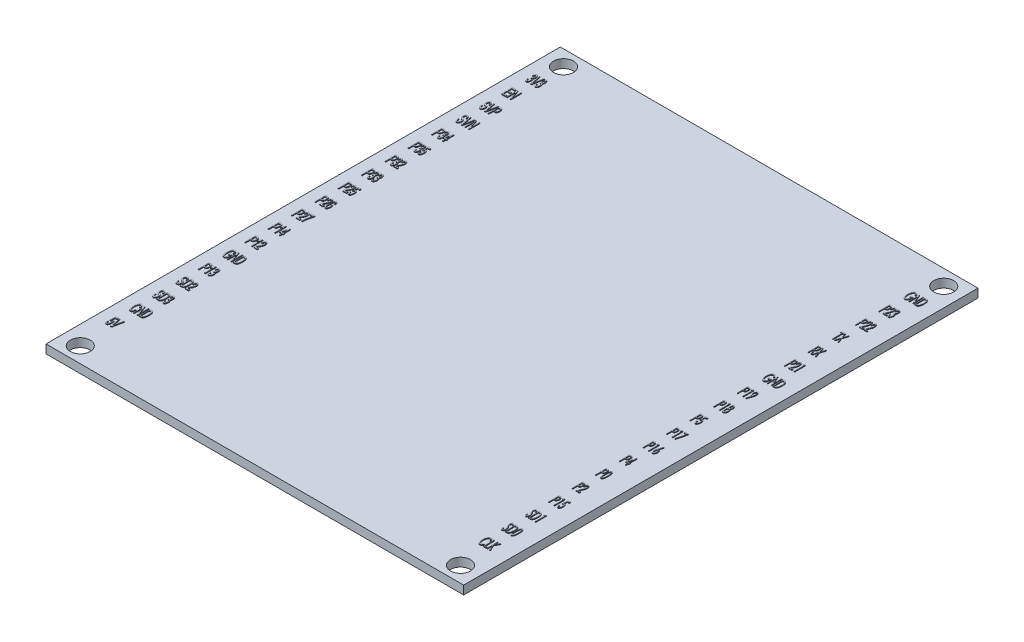
SolidWorks part; units mm, degrees
ref_plane "Front Plane" through (0, 0, 0) normal (0, 0, 1) x (1, 0, 0)
ref_plane "Top Plane" through (0, 0, 0) normal (0, 1, 0) x (1, 0, 0)
ref_plane "Right Plane" through (0, 0, 0) normal (1, 0, 0) x (0, 0, -1)
sketch "Sketch1" plane through (0, 0, 0) normal (0, 1, 0) x (1, 0, 0)
  line L1 (0, 0) -> (63.1, 0)
  line L2 (0, 0) -> (0, -77.7)
  line L3 (0, -77.7) -> (63.1, -77.7)
  line L4 (63.1, 0) -> (63.1, -77.7)
  dimension "D1" = 63.1
  dimension "D2" = 77.7
extrude "Boss-Extrude1" add sketch "Sketch1" along normal blind 1.3
sketch "Sketch2" plane through (0, 1.3, 0) normal (0, 1, 0) x (1, 0, 0)
  line L0 (0, 0) -> (1.5556, -1.5556) construction
  line L1 (0, -38.85) -> (63.1, -38.85) construction
  line L2 (0, 0) -> (0, -77.7) construction
  line L3 (63.1, -77.7) -> (63.1, 0) construction
  line L4 (31.55, -77.7) -> (31.55, 0) construction
  line L5 (0, -77.7) -> (63.1, -77.7) construction
  line L6 (63.1, 0) -> (0, 0) construction
  circle A0 centre (2.8308, -2.3456) radius 1.5
  circle A1 centre (2.8308, -75.3544) radius 1.5
  circle A2 centre (60.2692, -2.3456) radius 1.5
  circle A3 centre (60.2692, -75.3544) radius 1.5
  dimension "D2" = 3
  dimension "D1" = 2.2
extrude "Cut-Extrude1" cut sketch "Sketch2" against normal up to surface (1.3 mm away) up to face at (31.55, 0, 38.85)
sketch "Sketch3" plane through (0, 1.3, 0) normal (0, 1, 0) x (1, 0, 0)
  line L0 (63.1, -77.7) -> (63.1, 0) construction
  line L1 (58.6033, -7) -> (63.1, -7)
  text T0 "3V3\r\nEN\r\nSVP\r\nSVN\r\nP34\r\nP35\r\nP32\r\nP33\r\nP25\r\nP26\r\nP27\r\nP14\r\nP12\r\nGND\r\nP13\r\nSD2\r\nSD3\r\nCND\r\n5V" font "Arial" height 1.641
  text T1 "GND\r\nP23\r\nP22\r\nTX\r\nRX\r\nP21\r\nGND\r\nP19\r\nP18\r\nP5\r\nP17\r\nP16\r\nP4\r\nP0\r\nP2\r\nP15\r\nSD1\r\nSD0\r\nCLK" font "Century Gothic" height 1.6
sketch "Sketch4" plane through (0, 1.3, 0) normal (0, 1, 0) x (1, 0, 0)
  line L0 (58.8567, -7.1455) -> (1.6968, -7.1455) construction
  text T0 "3V3\r\nEN\r\nSVP\r\nSVN\r\nP34\r\nP35\r\nP32\r\nP33\r\nP25\r\nP26\r\nP27\r\nP14\r\nP12\r\nGND\r\nP13\r\nSD2\r\nSD3\r\nCND\r\n5V" font "Arial" height 1.641
  text T1 "GND\r\nP23\r\nP22\r\nTX\r\nRX\r\nP21\r\nGND\r\nP19\r\nP18\r\nP5\r\nP17\r\nP16\r\nP4\r\nP0\r\nP2\r\nP15\r\nSD1\r\nSD0\r\nCLK" font "Century Gothic" height 1.6
extrude "Boss-Extrude2" add sketch "Sketch4" along normal blind 0.1
